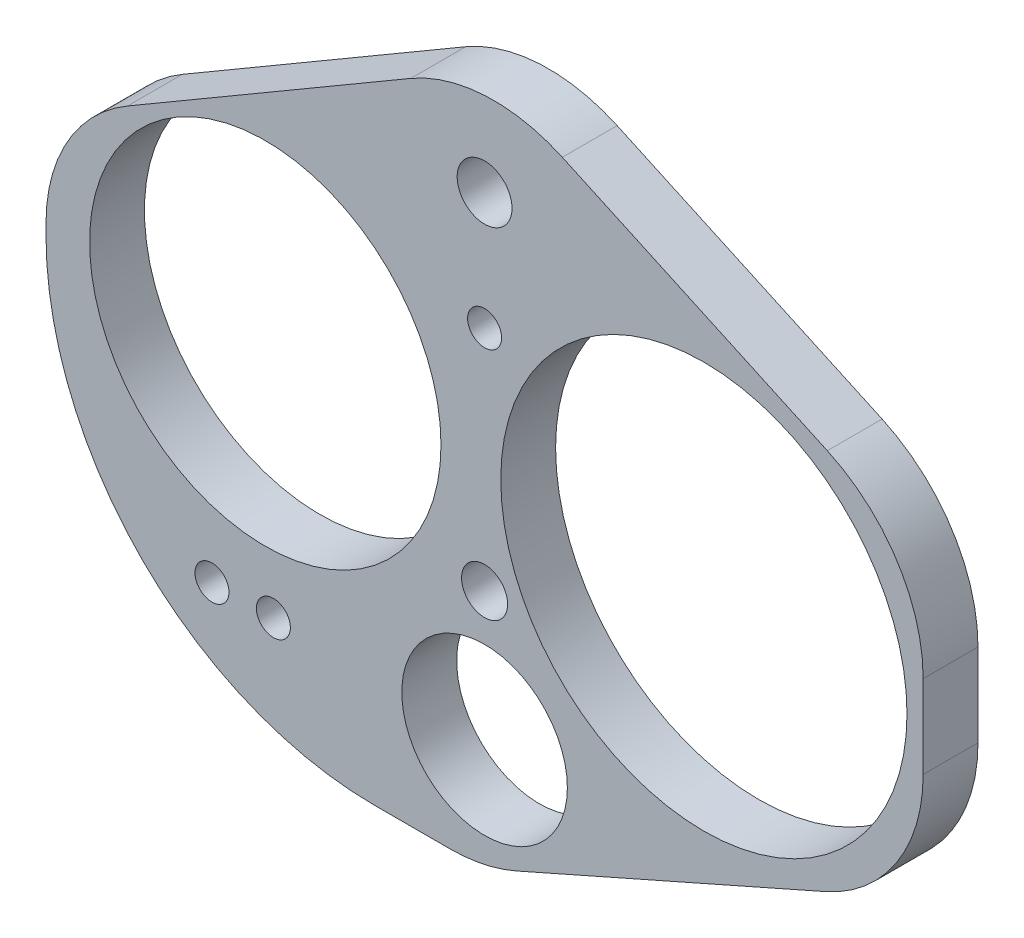
SolidWorks part; units mm, degrees
ref_plane "Front Plane" through (0, 0, 0) normal (0, 0, 1) x (1, 0, 0)
ref_plane "Top Plane" through (0, 0, 0) normal (0, 1, 0) x (1, 0, 0)
ref_plane "Right Plane" through (0, 0, 0) normal (1, 0, 0) x (0, 0, -1)
sketch "Sketch1" plane through (0, 0, 0) normal (0, 0, 1) x (1, 0, 0)
  line L0 (0, 0) -> (40, 0) construction
  line L1 (0.7371, -21.3168) -> (-4.8629, -21.3168)
  line L2 (-20, -31.5) -> (20, -31.5)
  line L3 (-20, -31.5) -> (-20, 8.1266)
  line L5 (60, -13.815) -> (60, 13.1418)
  line L6 (-20, -31.5) -> (60, 31.5) construction
  line L7 (-20, 31.5) -> (60, -31.5) construction
  line L8 (-20, 8.1266) -> (20, 31.5)
  line L9 (20, 31.5) -> (60, 13.1418)
  line L10 (60, -13.815) -> (20, -31.5)
  circle A0 centre (0, 0) radius 16.025
  circle A1 centre (40, 0) radius 18.525
  circle A2 centre (20, 11.209) radius 1.55
  circle A3 centre (20, -9.5571) radius 2.1
  circle A4 centre (20, 21.9186) radius 2.5
  circle A5 centre (20, -21.3168) radius 7.55
  circle A7 centre (0.7371, -21.3168) radius 1.55
  circle A8 centre (-4.8629, -21.3168) radius 1.55
  point P5 (20, 0)
  dimension "D1" = 32.05
  dimension "D2" = 37.05
  dimension "D6" = 3.1
  dimension "D7" = 4.2
  dimension "D8" = 5
  dimension "D9" = 15.1
  dimension "D12" = 3.1
  dimension "D13" = 3.1
  dimension "D3" = 40
  dimension "D4" = 80
  dimension "D5" = 63
  dimension "D11" = 5.6
extrude "Boss-Extrude1" add sketch "Sketch1" along normal blind 5 contours L2 L5 L3 A8 A7 A5 A4 A3 A2 A1 A0 region at (-18.9817, -11.6867, 0)
fillet "Fillet1" radius 15 5 edges at (60, -13.815, 2.5) (60, 13.1418, 2.5) (20, 31.5, 2.5) (-20, 8.1266, 2.5) (20, -31.5, 2.5)
fillet "Fillet2" radius 30 1 edges at (-20, -31.5, 2.5)
equation "\"RingPinShaft\"= 5"
equation "\"CenterBearingOut\"=32.05"
equation "\"RingPostIn\"=5.1"
equation "\"CamBearingOut\"=15.1"
equation "\"DiskOutputShaft\"=10.1"
equation "\"CenterShaft\"=25.2"
equation "\"Eccentricity\"=2"
equation "\"CycCamShaft\"=10.05"
equation "\"D1@Sketch1\"=\"CenterBearingOut\""
equation "\"OutputBearingOut\"=37.05"
equation "\"D2@Sketch1\"=\"OutputBearingOut\""
equation "\"D9@Sketch1\"=\"CamBearingOut\""
equation "\"D8@Sketch1\"=\"RingPinShaft\""
equation "\"m3Thru\"=3.1"
equation "\"m3Insert\"=4.2"
equation "\"D6@Sketch1\"=\"m3Thru\""
equation "\"D7@Sketch1\"=\"m3Insert\""
